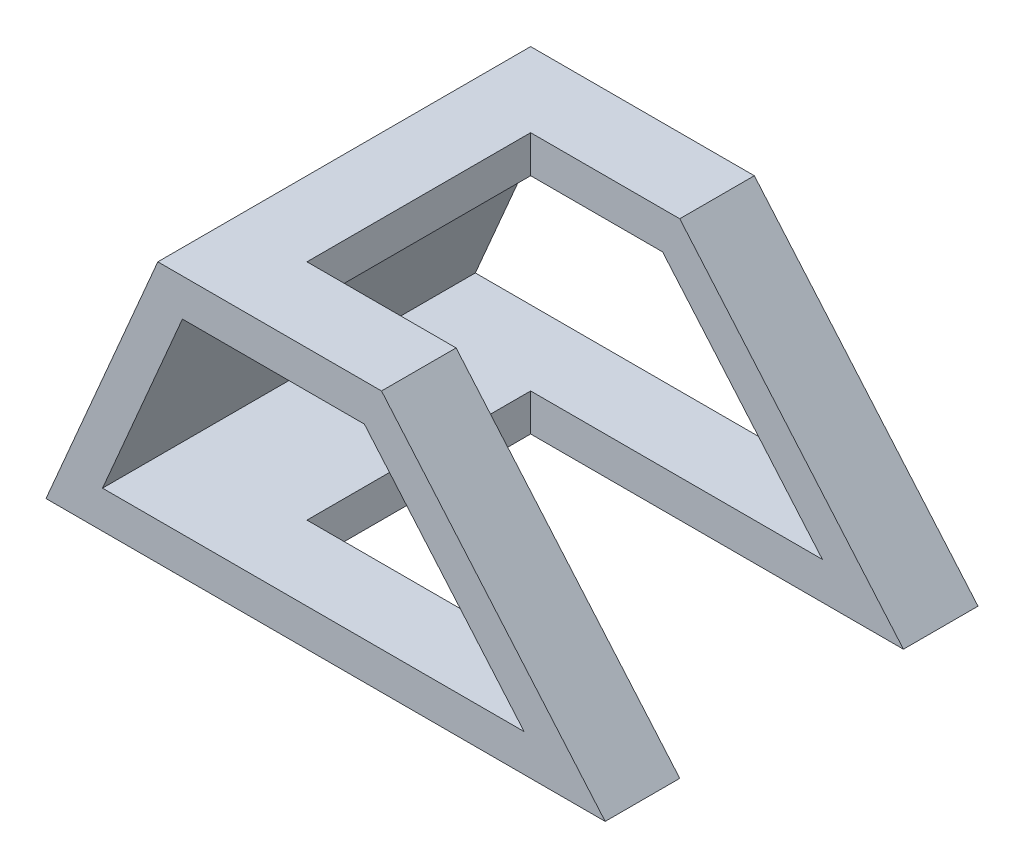
SolidWorks part; units mm, degrees
material "AISI 1020"
ref_plane "Front Plane" through (0, 0, 0) normal (0, 0, 1) x (1, 0, 0)
ref_plane "Top Plane" through (0, 0, 0) normal (0, 1, 0) x (1, 0, 0)
ref_plane "Right Plane" through (0, 0, 0) normal (1, 0, 0) x (0, 0, -1)
sketch "Esquisse3" plane through (0, 0, 0) normal (0, 0, 1) x (1, 0, 0)
  line L0 (0, 0) -> (150, 0)
  line L1 (150, 0) -> (90, 70)
  line L2 (90, 70) -> (30, 70)
  line L3 (30, 70) -> (0, 0)
  line L4 (36.594, 60) -> (15.1654, 10)
  line L5 (15.1654, 10) -> (128.2578, 10)
  line L6 (128.2578, 10) -> (85.4007, 60)
  line L7 (85.4007, 60) -> (36.594, 60)
  line L8 (50, 0) -> (50, 70)
  dimension "D1" = 150
  dimension "D2" = 60
  dimension "D3" = 60
  dimension "D4" = 10
  dimension "D5" = 70
  dimension "D6" = 100
extrude "Boss.-Extru.1" add sketch "Esquisse3" along normal mid plane 100 contours L0 L8 L5 L4 L7 L2 L3 | L8 L0 L1 L2 L7 L6 L5 region at (15.7907, 34.6611, 0) region at (51.2207, 5, 0)
extrude "Enlèv. mat.-Extru.1" cut sketch "Esquisse3<3>" against normal mid plane 60 contours L8 L0 L1 L2 L7 L6 L5 region at (51.2207, 5, 0)
sketch "Esquisse3<3>" plane through (0, 0, 0) normal (0, 0, 1) x (1, 0, 0) same geometry as "Esquisse3"
